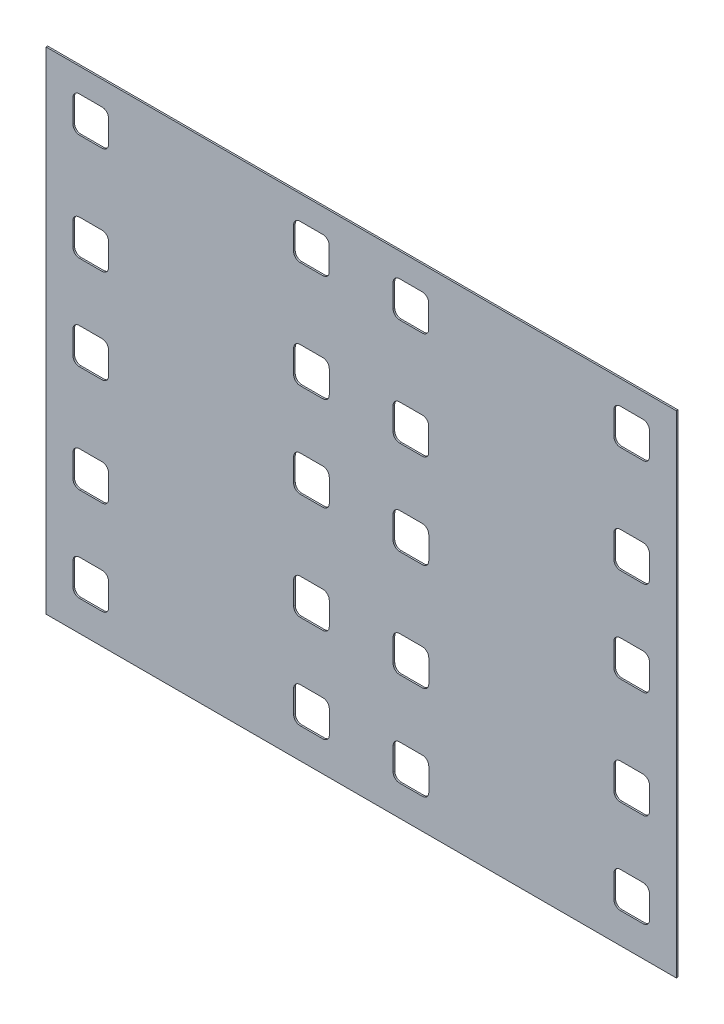
SolidWorks part; units mm, degrees
material "ABS"
ref_plane "X-Y Datum" through (0, 0, 0) normal (0, 0, 1) x (1, 0, 0)
ref_plane "X-Z Datum" through (0, 0, 0) normal (0, 1, 0) x (1, 0, 0)
ref_plane "Y-Z Datum" through (0, 0, 0) normal (1, 0, 0) x (0, 0, -1)
sketch "Sketch9" plane through (0, 0, 0) normal (0, 0, 1) x (1, 0, 0)
  line L0 (-82.7559, -182.5893) -> (-82.7583, -160.1613) construction
  line L1 (-89.109, -153.8119) -> (-111.537, -153.8143) construction
  line L2 (-117.8863, -160.165) -> (-117.8839, -182.593) construction
  line L3 (-111.5333, -188.9423) -> (-89.1053, -188.9399) construction
  line L4 (476.934, -311.4483) -> (476.8831, 172.8027)
  line L5 (476.8831, 172.8027) -> (-144.3755, 172.7375)
  line L6 (-144.3755, 172.7375) -> (-144.3246, -311.5135)
  line L7 (-144.3246, -311.5135) -> (476.934, -311.4483)
  line L8 (476.934, -311.4483) -> (476.8831, 172.8027)
  line L9 (476.8831, 172.8027) -> (-144.3755, 172.7375)
  line L10 (-144.3755, 172.7375) -> (-144.3246, -311.5135)
  line L11 (-144.3246, -311.5135) -> (476.934, -311.4483)
  line L12 (-111.5443, -83.8117) -> (-89.1163, -83.8093) construction
  line L13 (-82.767, -77.4587) -> (-82.7693, -55.0307) construction
  line L14 (-89.12, -48.6813) -> (-111.548, -48.6837) construction
  line L15 (-117.8973, -55.0344) -> (-117.895, -77.4624) construction
  line L16 (-82.7877, 120.2549) -> (-82.7901, 142.6829) construction
  line L17 (-89.1408, 149.0323) -> (-111.5688, 149.0299) construction
  line L18 (-117.9181, 142.6792) -> (-117.9157, 120.2512) construction
  line L19 (-111.5651, 113.9019) -> (-89.1371, 113.9043) construction
  line L20 (-111.554, 8.7713) -> (-89.126, 8.7737) construction
  line L21 (-117.9071, 37.5486) -> (-117.9047, 15.1206) construction
  line L22 (-89.1297, 43.9017) -> (-111.5577, 43.8993) construction
  line L23 (-82.7767, 15.1243) -> (-82.7791, 37.5523) construction
  line L24 (-82.7559, -182.5893) -> (-82.7583, -160.1613)
  line L25 (-89.109, -153.8119) -> (-111.537, -153.8143)
  line L26 (-117.8863, -160.165) -> (-117.8839, -182.593)
  line L27 (-111.5333, -188.9423) -> (-89.1053, -188.9399)
  line L28 (-111.5443, -83.8117) -> (-89.1163, -83.8093)
  line L29 (-82.767, -77.4587) -> (-82.7693, -55.0307)
  line L30 (-89.12, -48.6813) -> (-111.548, -48.6837)
  line L31 (-117.8973, -55.0344) -> (-117.895, -77.4624)
  line L32 (-82.7877, 120.2549) -> (-82.7901, 142.6829)
  line L33 (-89.1408, 149.0323) -> (-111.5688, 149.0299)
  line L34 (-117.9181, 142.6792) -> (-117.9157, 120.2512)
  line L35 (-111.5651, 113.9019) -> (-89.1371, 113.9043)
  line L36 (-111.554, 8.7713) -> (-89.126, 8.7737)
  line L37 (-117.9071, 37.5486) -> (-117.9047, 15.1206)
  line L38 (-89.1297, 43.9017) -> (-111.5577, 43.8993)
  line L39 (-82.7767, 15.1243) -> (-82.7791, 37.5523)
  line L40 (-82.7462, -275.1723) -> (-82.7486, -252.7443) construction
  line L41 (-89.0992, -246.3949) -> (-111.5272, -246.3973) construction
  line L42 (-117.8766, -252.748) -> (-117.8742, -275.176) construction
  line L43 (-111.5235, -281.5253) -> (-89.0955, -281.5229) construction
  line L44 (-82.7462, -275.1723) -> (-82.7486, -252.7443)
  line L45 (-89.0992, -246.3949) -> (-111.5272, -246.3973)
  line L46 (-117.8766, -252.748) -> (-117.8742, -275.176)
  line L47 (-111.5235, -281.5253) -> (-89.0955, -281.5229)
  arc A0 (-89.1053, -188.9399) -> (-82.7559, -182.5893) centre (-89.1059, -182.5899) ccw construction
  arc A1 (-82.7583, -160.1613) -> (-89.109, -153.8119) centre (-89.1083, -160.1619) ccw construction
  arc A2 (-111.537, -153.8143) -> (-117.8863, -160.165) centre (-111.5363, -160.1643) ccw construction
  arc A3 (-117.8839, -182.593) -> (-111.5333, -188.9423) centre (-111.5339, -182.5923) ccw construction
  arc A4 (-89.1163, -83.8093) -> (-82.767, -77.4587) centre (-89.117, -77.4593) ccw construction
  arc A5 (-82.7693, -55.0307) -> (-89.12, -48.6813) centre (-89.1193, -55.0313) ccw construction
  arc A6 (-111.548, -48.6837) -> (-117.8973, -55.0344) centre (-111.5473, -55.0337) ccw construction
  arc A7 (-117.895, -77.4624) -> (-111.5443, -83.8117) centre (-111.545, -77.4617) ccw construction
  arc A8 (-89.1371, 113.9043) -> (-82.7877, 120.2549) centre (-89.1377, 120.2543) ccw construction
  arc A9 (-82.7901, 142.6829) -> (-89.1408, 149.0323) centre (-89.1401, 142.6823) ccw construction
  arc A10 (-111.5688, 149.0299) -> (-117.9181, 142.6792) centre (-111.5681, 142.6799) ccw construction
  arc A11 (-117.9157, 120.2512) -> (-111.5651, 113.9019) centre (-111.5657, 120.2519) ccw construction
  arc A12 (-82.7791, 37.5523) -> (-89.1297, 43.9017) centre (-89.1291, 37.5517) ccw construction
  arc A13 (-89.126, 8.7737) -> (-82.7767, 15.1243) centre (-89.1267, 15.1237) ccw construction
  arc A14 (-117.9047, 15.1206) -> (-111.554, 8.7713) centre (-111.5547, 15.1213) ccw construction
  arc A15 (-111.5577, 43.8993) -> (-117.9071, 37.5486) centre (-111.5571, 37.5493) ccw construction
  arc A16 (-89.1053, -188.9399) -> (-82.7559, -182.5893) centre (-89.1059, -182.5899) ccw
  arc A17 (-82.7583, -160.1613) -> (-89.109, -153.8119) centre (-89.1083, -160.1619) ccw
  arc A18 (-111.537, -153.8143) -> (-117.8863, -160.165) centre (-111.5363, -160.1643) ccw
  arc A19 (-117.8839, -182.593) -> (-111.5333, -188.9423) centre (-111.5339, -182.5923) ccw
  arc A20 (-89.1163, -83.8093) -> (-82.767, -77.4587) centre (-89.117, -77.4593) ccw
  arc A21 (-82.7693, -55.0307) -> (-89.12, -48.6813) centre (-89.1193, -55.0313) ccw
  arc A22 (-111.548, -48.6837) -> (-117.8973, -55.0344) centre (-111.5473, -55.0337) ccw
  arc A23 (-117.895, -77.4624) -> (-111.5443, -83.8117) centre (-111.545, -77.4617) ccw
  arc A24 (-89.1371, 113.9043) -> (-82.7877, 120.2549) centre (-89.1377, 120.2543) ccw
  arc A25 (-82.7901, 142.6829) -> (-89.1408, 149.0323) centre (-89.1401, 142.6823) ccw
  arc A26 (-111.5688, 149.0299) -> (-117.9181, 142.6792) centre (-111.5681, 142.6799) ccw
  arc A27 (-117.9157, 120.2512) -> (-111.5651, 113.9019) centre (-111.5657, 120.2519) ccw
  arc A28 (-82.7791, 37.5523) -> (-89.1297, 43.9017) centre (-89.1291, 37.5517) ccw
  arc A29 (-89.126, 8.7737) -> (-82.7767, 15.1243) centre (-89.1267, 15.1237) ccw
  arc A30 (-117.9047, 15.1206) -> (-111.554, 8.7713) centre (-111.5547, 15.1213) ccw
  arc A31 (-111.5577, 43.8993) -> (-117.9071, 37.5486) centre (-111.5571, 37.5493) ccw
  arc A32 (-89.0955, -281.5229) -> (-82.7462, -275.1723) centre (-89.0962, -275.1729) ccw construction
  arc A33 (-111.5272, -246.3973) -> (-117.8766, -252.748) centre (-111.5266, -252.7473) ccw construction
  arc A34 (-117.8742, -275.176) -> (-111.5235, -281.5253) centre (-111.5242, -275.1753) ccw construction
  arc A35 (-89.0955, -281.5229) -> (-82.7462, -275.1723) centre (-89.0962, -275.1729) ccw
  arc A36 (-111.5272, -246.3973) -> (-117.8766, -252.748) centre (-111.5266, -252.7473) ccw
  arc A37 (-117.8742, -275.176) -> (-111.5235, -281.5253) centre (-111.5242, -275.1753) ccw
  arc A38 (-82.7486, -252.7443) -> (-89.0992, -246.3949) centre (-89.0986, -252.7449) ccw construction
  arc A39 (-82.7486, -252.7443) -> (-89.0992, -246.3949) centre (-89.0986, -252.7449) ccw
  dimension "D1" = 0
extrude "Boss-Extrude2" add sketch "Sketch9" along normal blind 1.5875 contours L10 L11 L8 L9 A39 L44 A35 L47 A37 L46 A36 L45 A31 L38 A28 L39 A29 L36 A30 L37 A27 L34 A26 L33 A25 L32 A24 L35 A23 L31 A22 L30 A21 L29 A20 L28 A19 L26 A18 L25 A17 L24 A16 L27 | L44 A39 L45 A36 L46 A37 L47 A35 | L26 A19 L27 A16 L24 A17 L25 A18 | L38 A31 L37 A30 L36 A29 L39 A28 | L34 A27 L35 A24 L32 A25 L33 A26 | L31 A23 L28 A20 L29 A21 L30 A22 region at (171.7018, -69.3676, 0) region at (-100.3211, -171.3771, 0) region at (-100.3322, -66.2465, 0) region at (-100.3529, 131.4671, 0) region at (-100.3419, 26.3365, 0) region at (-100.3114, -263.9601, 0)
sketch "Sketch10" plane through (0, 0, 1.5875) normal (0, 0, 1) x (1, 0, 0)
  line L4 (476.934, -311.4483) -> (476.8831, 172.8027)
  line L5 (476.8831, 172.8027) -> (-144.3755, 172.7375)
  line L6 (-144.3755, 172.7375) -> (-144.3246, -311.5135)
  line L7 (-144.3246, -311.5135) -> (476.934, -311.4483)
  line L8 (476.934, -311.4483) -> (476.8831, 172.8027)
  line L9 (476.8831, 172.8027) -> (-144.3755, 172.7375)
  line L10 (-144.3755, 172.7375) -> (-144.3246, -311.5135)
  line L11 (-144.3246, -311.5135) -> (476.934, -311.4483)
  line L12 (-117.8863, -160.165) -> (-117.8839, -182.593)
  line L13 (-111.5333, -188.9423) -> (-89.1053, -188.9399)
  line L14 (-82.7559, -182.5893) -> (-82.7583, -160.1613)
  line L15 (-89.109, -153.8119) -> (-111.537, -153.8143)
  line L16 (-117.8863, -160.165) -> (-117.8839, -182.593)
  line L17 (-111.5333, -188.9423) -> (-89.1053, -188.9399)
  line L18 (-82.7559, -182.5893) -> (-82.7583, -160.1613)
  line L19 (-89.109, -153.8119) -> (-111.537, -153.8143)
  line L20 (-117.8766, -252.748) -> (-117.8742, -275.176)
  line L21 (-89.0992, -246.3949) -> (-111.5272, -246.3973)
  line L22 (-82.7462, -275.1723) -> (-82.7486, -252.7443)
  line L23 (-111.5235, -281.5253) -> (-89.0955, -281.5229)
  line L24 (-117.8766, -252.748) -> (-117.8742, -275.176)
  line L25 (-89.0992, -246.3949) -> (-111.5272, -246.3973)
  line L26 (-82.7462, -275.1723) -> (-82.7486, -252.7443)
  line L27 (-111.5235, -281.5253) -> (-89.0955, -281.5229)
  line L28 (-89.12, -48.6813) -> (-111.548, -48.6837)
  line L29 (-117.8973, -55.0344) -> (-117.895, -77.4624)
  line L30 (-111.5443, -83.8117) -> (-89.1163, -83.8093)
  line L31 (-82.767, -77.4587) -> (-82.7693, -55.0307)
  line L32 (-89.12, -48.6813) -> (-111.548, -48.6837)
  line L33 (-117.8973, -55.0344) -> (-117.895, -77.4624)
  line L34 (-111.5443, -83.8117) -> (-89.1163, -83.8093)
  line L35 (-82.767, -77.4587) -> (-82.7693, -55.0307)
  line L36 (-82.7877, 120.2549) -> (-82.7901, 142.6829)
  line L37 (-111.5651, 113.9019) -> (-89.1371, 113.9043)
  line L38 (-117.9181, 142.6792) -> (-117.9157, 120.2512)
  line L39 (-89.1408, 149.0323) -> (-111.5688, 149.0299)
  line L40 (-82.7877, 120.2549) -> (-82.7901, 142.6829)
  line L41 (-111.5651, 113.9019) -> (-89.1371, 113.9043)
  line L42 (-117.9181, 142.6792) -> (-117.9157, 120.2512)
  line L43 (-89.1408, 149.0323) -> (-111.5688, 149.0299)
  line L44 (-111.554, 8.7713) -> (-89.126, 8.7737)
  line L45 (-82.7767, 15.1243) -> (-82.7791, 37.5523)
  line L46 (-89.1297, 43.9017) -> (-111.5577, 43.8993)
  line L47 (-117.9071, 37.5486) -> (-117.9047, 15.1206)
  line L48 (-111.554, 8.7713) -> (-89.126, 8.7737)
  line L49 (-82.7767, 15.1243) -> (-82.7791, 37.5523)
  line L50 (-89.1297, 43.9017) -> (-111.5577, 43.8993)
  line L51 (-117.9071, 37.5486) -> (-117.9047, 15.1206)
  arc A4 (-117.8839, -182.593) -> (-111.5333, -188.9423) centre (-111.5339, -182.5923) ccw
  arc A5 (-89.1053, -188.9399) -> (-82.7559, -182.5893) centre (-89.1059, -182.5899) ccw
  arc A6 (-82.7583, -160.1613) -> (-89.109, -153.8119) centre (-89.1083, -160.1619) ccw
  arc A7 (-111.537, -153.8143) -> (-117.8863, -160.165) centre (-111.5363, -160.1643) ccw
  arc A8 (-117.8839, -182.593) -> (-111.5333, -188.9423) centre (-111.5339, -182.5923) ccw
  arc A9 (-89.1053, -188.9399) -> (-82.7559, -182.5893) centre (-89.1059, -182.5899) ccw
  arc A10 (-82.7583, -160.1613) -> (-89.109, -153.8119) centre (-89.1083, -160.1619) ccw
  arc A11 (-111.537, -153.8143) -> (-117.8863, -160.165) centre (-111.5363, -160.1643) ccw
  arc A12 (-111.5272, -246.3973) -> (-117.8766, -252.748) centre (-111.5266, -252.7473) ccw
  arc A13 (-82.7486, -252.7443) -> (-89.0992, -246.3949) centre (-89.0986, -252.7449) ccw
  arc A14 (-89.0955, -281.5229) -> (-82.7462, -275.1723) centre (-89.0962, -275.1729) ccw
  arc A15 (-117.8742, -275.176) -> (-111.5235, -281.5253) centre (-111.5242, -275.1753) ccw
  arc A16 (-111.5272, -246.3973) -> (-117.8766, -252.748) centre (-111.5266, -252.7473) ccw
  arc A17 (-82.7486, -252.7443) -> (-89.0992, -246.3949) centre (-89.0986, -252.7449) ccw
  arc A18 (-89.0955, -281.5229) -> (-82.7462, -275.1723) centre (-89.0962, -275.1729) ccw
  arc A19 (-117.8742, -275.176) -> (-111.5235, -281.5253) centre (-111.5242, -275.1753) ccw
  arc A20 (-111.548, -48.6837) -> (-117.8973, -55.0344) centre (-111.5473, -55.0337) ccw
  arc A21 (-117.895, -77.4624) -> (-111.5443, -83.8117) centre (-111.545, -77.4617) ccw
  arc A22 (-89.1163, -83.8093) -> (-82.767, -77.4587) centre (-89.117, -77.4593) ccw
  arc A23 (-82.7693, -55.0307) -> (-89.12, -48.6813) centre (-89.1193, -55.0313) ccw
  arc A24 (-111.548, -48.6837) -> (-117.8973, -55.0344) centre (-111.5473, -55.0337) ccw
  arc A25 (-117.895, -77.4624) -> (-111.5443, -83.8117) centre (-111.545, -77.4617) ccw
  arc A26 (-89.1163, -83.8093) -> (-82.767, -77.4587) centre (-89.117, -77.4593) ccw
  arc A27 (-82.7693, -55.0307) -> (-89.12, -48.6813) centre (-89.1193, -55.0313) ccw
  arc A28 (-89.1371, 113.9043) -> (-82.7877, 120.2549) centre (-89.1377, 120.2543) ccw
  arc A29 (-117.9157, 120.2512) -> (-111.5651, 113.9019) centre (-111.5657, 120.2519) ccw
  arc A30 (-111.5688, 149.0299) -> (-117.9181, 142.6792) centre (-111.5681, 142.6799) ccw
  arc A31 (-82.7901, 142.6829) -> (-89.1408, 149.0323) centre (-89.1401, 142.6823) ccw
  arc A32 (-89.1371, 113.9043) -> (-82.7877, 120.2549) centre (-89.1377, 120.2543) ccw
  arc A33 (-117.9157, 120.2512) -> (-111.5651, 113.9019) centre (-111.5657, 120.2519) ccw
  arc A34 (-111.5688, 149.0299) -> (-117.9181, 142.6792) centre (-111.5681, 142.6799) ccw
  arc A35 (-82.7901, 142.6829) -> (-89.1408, 149.0323) centre (-89.1401, 142.6823) ccw
  arc A36 (-89.126, 8.7737) -> (-82.7767, 15.1243) centre (-89.1267, 15.1237) ccw
  arc A37 (-82.7791, 37.5523) -> (-89.1297, 43.9017) centre (-89.1291, 37.5517) ccw
  arc A38 (-111.5577, 43.8993) -> (-117.9071, 37.5486) centre (-111.5571, 37.5493) ccw
  arc A39 (-117.9047, 15.1206) -> (-111.554, 8.7713) centre (-111.5547, 15.1213) ccw
  arc A40 (-89.126, 8.7737) -> (-82.7767, 15.1243) centre (-89.1267, 15.1237) ccw
  arc A41 (-82.7791, 37.5523) -> (-89.1297, 43.9017) centre (-89.1291, 37.5517) ccw
  arc A42 (-111.5577, 43.8993) -> (-117.9071, 37.5486) centre (-111.5571, 37.5493) ccw
  arc A43 (-117.9047, 15.1206) -> (-111.554, 8.7713) centre (-111.5547, 15.1213) ccw
  dimension "D1" = 0
  dimension "D2" = 0
  dimension "D3" = 0
  dimension "D4" = 0
  dimension "D5" = 0
  dimension "D6" = 0
extrude "Cut-Extrude6" cut sketch "Sketch10" against normal through all contours L40 A35 L43 A34 L42 A33 L41 A32 | L51 A43 L48 A40 L49 A41 L50 A42 | L35 A27 L32 A24 L33 A25 L34 A26 | L19 A11 L16 A8 L17 A9 L18 A10 | L24 A19 L27 A18 L26 A17 L25 A16 region at (-100.3211, -171.3771, 1.5875) region at (-100.3114, -263.9601, 1.5875) region at (-100.3322, -66.2465, 1.5875) region at (-100.3529, 131.4671, 1.5875) region at (-100.3419, 26.3365, 1.5875)
pattern_linear "LPattern2" count 2 spacing 217.5764 along (1, 0.0001, 0) of "Cut-Extrude6"
ref_plane "Plane1" through (166.272, 0.0175, 0) normal (-1, -0.0001, 0) x (0, 0, 1)
mirror "Mirror1" about plane through (166.272, 0.0175, 0) normal (-1, -0.0001, 0) of "LPattern2", "Cut-Extrude6"
